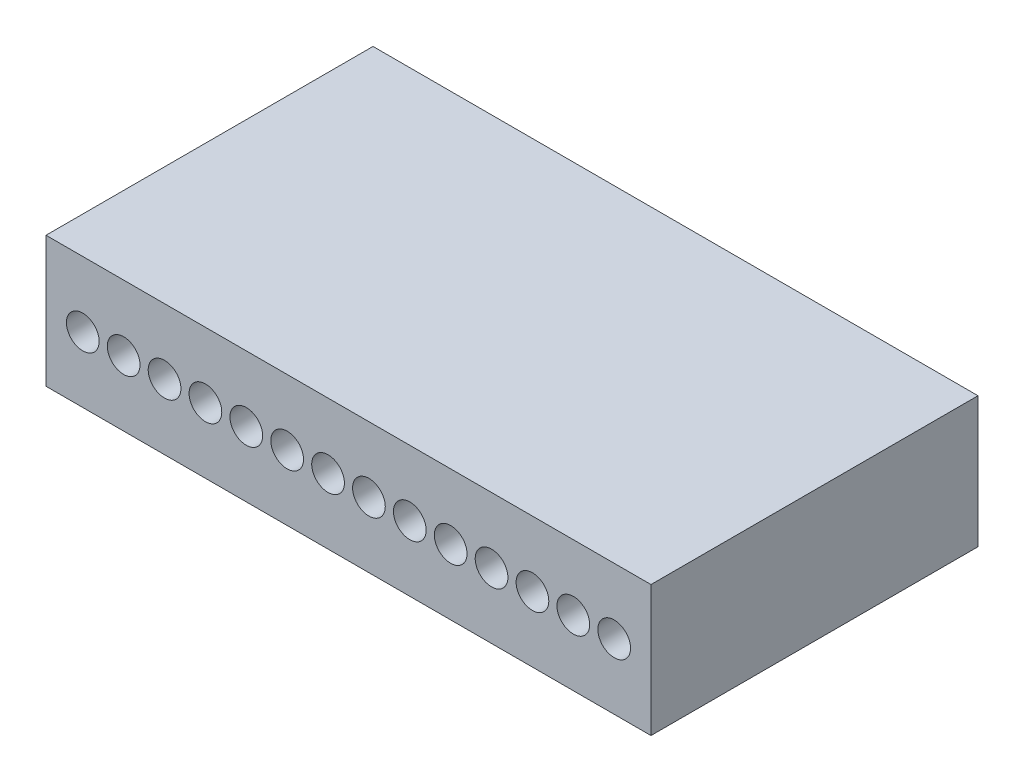
SolidWorks part; units mm, degrees
ref_plane "Front Plane" through (0, 0, 0) normal (0, 0, 1) x (1, 0, 0)
ref_plane "Top Plane" through (0, 0, 0) normal (0, 1, 0) x (1, 0, 0)
ref_plane "Right Plane" through (0, 0, 0) normal (1, 0, 0) x (0, 0, -1)
sketch "Sketch2" plane through (0, 0, 0) normal (0, 0, 1) x (1, 0, 0)
  line L1 (0, 0) -> (18.5, 0)
  line L2 (0, 0) -> (0, 4)
  line L3 (0, 4) -> (18.5, 4)
  line L4 (18.5, 0) -> (18.5, 4)
  dimension "D1" = 18.5
  dimension "D2" = 4
extrude "Boss-Extrude1" add sketch "Sketch2" along normal blind 10
sketch "Sketch3" plane through (0, 0, 10) normal (0, 0, 1) x (1, 0, 0)
  line L0 (0, 2) -> (18.5, 2) construction
  line L1 (0, 4) -> (0, 0) construction
  line L2 (18.5, 0) -> (18.5, 4) construction
  line L3 (0, 2) -> (18.5, 2) construction
  line L4 (18.5, 4) -> (0, 4) construction
  line L5 (0, 0) -> (18.5, 0) construction
  line L6 (1.125, 4) -> (1.125, 0) construction
  circle A0 centre (1.125, 2) radius 0.5
  circle A1 centre (2.375, 2) radius 0.5
  circle A2 centre (3.625, 2) radius 0.5
  circle A3 centre (4.875, 2) radius 0.5
  circle A4 centre (6.125, 2) radius 0.5
  circle A5 centre (7.375, 2) radius 0.5
  circle A6 centre (8.625, 2) radius 0.5
  circle A7 centre (9.875, 2) radius 0.5
  circle A8 centre (11.125, 2) radius 0.5
  circle A9 centre (12.375, 2) radius 0.5
  circle A10 centre (13.625, 2) radius 0.5
  circle A11 centre (14.875, 2) radius 0.5
  circle A12 centre (16.125, 2) radius 0.5
  circle A13 centre (17.375, 2) radius 0.5
  circle A21 centre (24.875, 2) radius 0.5 [skipped]
  circle A22 centre (23.625, 2) radius 0.5 [skipped]
  circle A23 centre (22.375, 2) radius 0.5 [skipped]
  circle A24 centre (21.125, 2) radius 0.5 [skipped]
  circle A25 centre (19.875, 2) radius 0.5 [skipped]
  circle A26 centre (18.625, 2) radius 0.5 [skipped]
  dimension "D1" = 1
  dimension "D2" = 2
  dimension "D3" = 1.125
  dimension "D5" = 1.25
  dimension "D4" = 20
extrude "Cut-Extrude1" cut sketch "Sketch3" against normal blind 5
sketch "Sketch4" plane through (0, 0, 10) normal (0, 0, 1) x (1, 0, 0)
  point P0 (1.125, 2)
  point P1 (2.375, 2)
  point P3 (3.625, 2)
  point P5 (4.875, 2)
  point P7 (6.125, 2)
  point P9 (7.375, 2)
  point P11 (8.625, 2)
  point P13 (9.875, 2)
  point P15 (11.125, 2)
  point P17 (12.375, 2)
  point P19 (13.625, 2)
  point P21 (14.875, 2)
  point P23 (16.125, 2)
  point P25 (17.375, 2)
other "CPoint1" parameters "Diameter"=25.4, "StubLength"=38.1
ref_axis "Axis1" through (1.125, 2, 20) along (0, 0, -1)
other "CPoint2" parameters "Diameter"=25.4, "StubLength"=38.1
ref_axis "Axis2" through (2.375, 2, 20) along (0, 0, -1)
other "CPoint3" parameters "Diameter"=25.4, "StubLength"=38.1
ref_axis "Axis3" through (3.625, 2, 20) along (0, 0, -1)
other "CPoint4" parameters "Diameter"=25.4, "StubLength"=38.1
ref_axis "Axis4" through (4.875, 2, 20) along (0, 0, -1)
other "CPoint5" parameters "Diameter"=25.4, "StubLength"=38.1
ref_axis "Axis5" through (6.125, 2, 20) along (0, 0, -1)
other "CPoint6" parameters "Diameter"=25.4, "StubLength"=38.1
ref_axis "Axis6" through (7.375, 2, 20) along (0, 0, -1)
other "CPoint7" parameters "Diameter"=25.4, "StubLength"=38.1
ref_axis "Axis7" through (8.625, 2, 20) along (0, 0, -1)
other "CPoint8" parameters "Diameter"=25.4, "StubLength"=38.1
ref_axis "Axis8" through (9.875, 2, 20) along (0, 0, -1)
other "CPoint9"
ref_axis "Axis9" through (11.125, 2, 20) along (0, 0, -1)
other "CPoint10"
ref_axis "Axis10" through (12.375, 2, 20) along (0, 0, -1)
other "CPoint11"
ref_axis "Axis11" through (13.625, 2, 20) along (0, 0, -1)
other "CPoint12"
ref_axis "Axis12" through (14.875, 2, 20) along (0, 0, -1)
other "CPoint13"
ref_axis "Axis13" through (16.125, 2, 20) along (0, 0, -1)
other "CPoint14"
ref_axis "Axis14" through (17.375, 2, 20) along (0, 0, -1)
